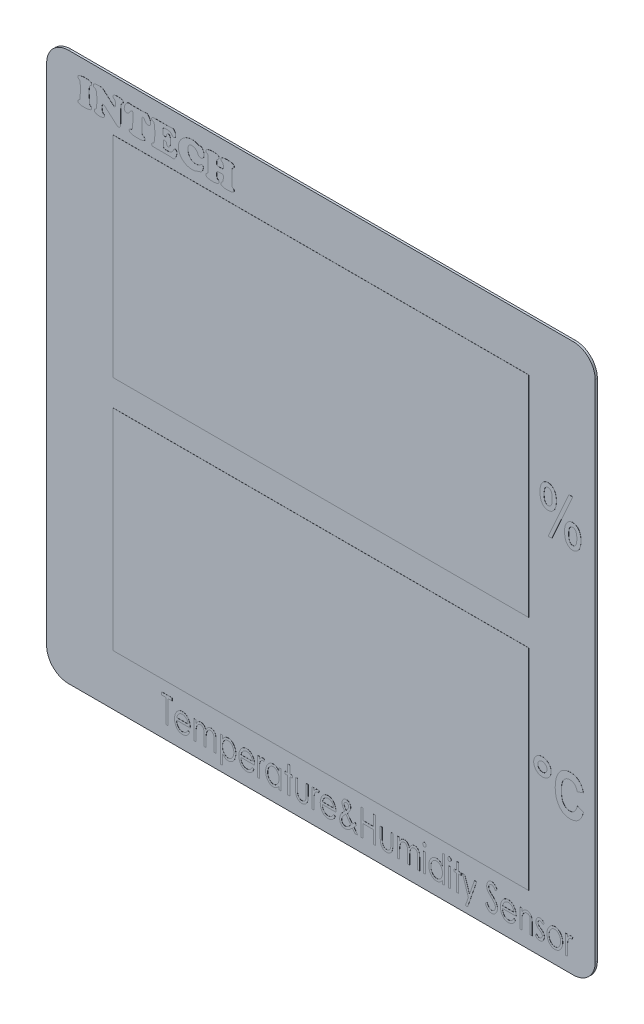
SolidWorks part; units mm, degrees
ref_plane "Front Plane" through (0, 0, 0) normal (0, 0, 1) x (1, 0, 0)
ref_plane "Top Plane" through (0, 0, 0) normal (0, 1, 0) x (1, 0, 0)
ref_plane "Right Plane" through (0, 0, 0) normal (1, 0, 0) x (0, 0, -1)
sketch "Sketch1" plane through (0, 0, 0) normal (0, 0, 1) x (1, 0, 0)
  line L0 (-25, 23) -> (-25, -23)
  line L1 (-23, -25) -> (23, -25)
  line L2 (25, -23) -> (25, 23)
  line L3 (23, 25) -> (-23, 25)
  line L4 (-25, 0) -> (25, 0) construction
  line L5 (0, 25) -> (0, -25) construction
  arc A0 (-25, -23) -> (-23, -25) centre (-23, -23) ccw
  arc A1 (23, -25) -> (25, -23) centre (23, -23) ccw
  arc A2 (25, 23) -> (23, 25) centre (23, 23) ccw
  arc A3 (-23, 25) -> (-25, 23) centre (-23, 23) ccw
extrude "Boss-Extrude1" add sketch "Sketch1" along normal blind 0.2
sketch "Sketch2" plane through (0, 0, 0.2) normal (0, 0, 1) x (1, 0, 0)
  line L0 (-21.85, -21.85) -> (21.85, -21.85) construction
  line L1 (21.85, -21.85) -> (21.85, 21.85) construction
  line L2 (21.85, 21.85) -> (-21.85, 21.85) construction
  line L3 (-21.85, 21.85) -> (-21.85, -21.85) construction
  line L4 (0, -21.85) -> (0, 21.85) construction
  line L5 (-21.85, 0) -> (21.85, 0) construction
  line L6 (21.85, 20.35) -> (-21.85, 20.35) construction
  line L7 (18.95, -21.85) -> (18.95, 21.85) construction
  line L8 (-21.85, -20.35) -> (21.85, -20.35) construction
  line L9 (-21.85, -1.2) -> (21.85, -1.2) construction
  line L10 (-18.95, -21.85) -> (-18.95, 21.85) construction
  line L11 (-21.85, 1.2) -> (21.85, 1.2) construction
  line L12 (0, -1.2) -> (-18.95, -1.2)
  line L13 (-18.95, -1.2) -> (-18.95, -20.35)
  line L14 (-18.95, -20.35) -> (18.95, -20.35)
  line L15 (18.95, -20.35) -> (18.95, -1.2)
  line L16 (18.95, -1.2) -> (0, -1.2)
  line L17 (-18.95, 1.2) -> (-18.95, 20.35)
  line L18 (-18.95, 20.35) -> (18.95, 20.35)
  line L19 (18.95, 20.35) -> (18.95, 1.2)
  line L20 (18.95, 1.2) -> (-18.95, 1.2)
extrude "Boss-Extrude2" add sketch "Sketch2" along normal blind 0.01 and the other way blind 0.2
sketch "Sketch3" plane through (0, 0, 0.2) normal (0, 0, 1) x (1, 0, 0)
  text T0 "<b>°C</b>" font "Arial Narrow" height in points 14
extrude "Boss-Extrude3" add sketch "Sketch3" along normal blind 0.01
sketch "Sketch4" plane through (0, 0, 0.2) normal (0, 0, 1) x (1, 0, 0)
  text T0 "%" font "Arial Narrow" height in points 16
extrude "Boss-Extrude4" add sketch "Sketch4" along normal blind 0.01
sketch "Sketch5" plane through (0, 0, 0.2) normal (0, 0, 1) x (1, 0, 0)
  text T0 "Temperature&Humidity Sensor" font "Century Gothic" height in points 9
extrude "Boss-Extrude5" add sketch "Sketch5" along normal blind 0.01
sketch "Sketch6" plane through (0, 0, 0.2) normal (0, 0, 1) x (1, 0, 0)
  text T0 "INTECH" font "Cooper Black" height in points 10
extrude "Boss-Extrude6" add sketch "Sketch6" along normal blind 0.01
